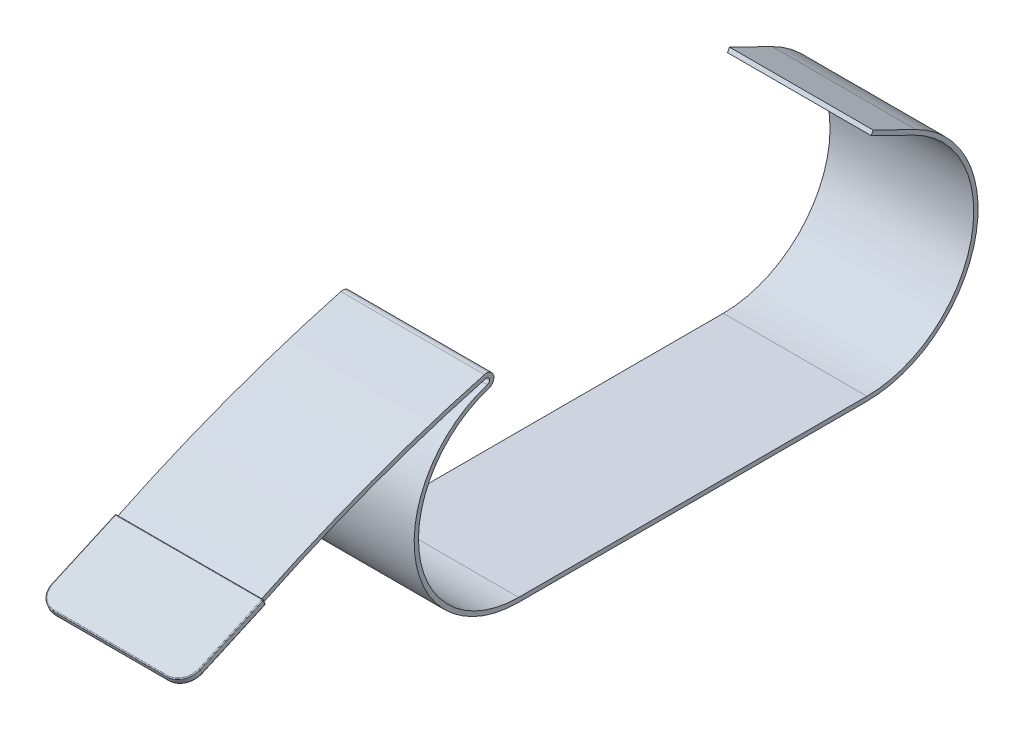
SolidWorks part; units mm, degrees
ref_plane "Front Plane" through (0, 0, 0) normal (0, 0, 1) x (1, 0, 0)
ref_plane "Top Plane" through (0, 0, 0) normal (0, 1, 0) x (1, 0, 0)
ref_plane "Right Plane" through (0, 0, 0) normal (1, 0, 0) x (0, 0, -1)
sketch "Sketch1" plane through (0, 0, 0) normal (1, 0, 0) x (0, 0, -1)
  line L0 (-20, 0) -> (20, 0)
  line L4 (25.3925, 23.2696) -> (20.4877, 25.6719)
  line L5 (-20, -0.5) -> (20, -0.5)
  line L6 (25.6124, 23.7187) -> (20.7076, 26.121)
  line L7 (-49.7729, 14.4908) -> (-49.5556, 14.0405)
  line L8 (20.7076, 26.121) -> (20.4877, 25.6719)
  arc A0 (20, 0) -> (25.3925, 23.2696) centre (20, 12.2596) ccw
  arc A1 (-20, 0) -> (-23.4407, 22.4768) centre (-20, 11.5018) cw
  arc A2 (-23.4407, 22.4768) -> (-23.9201, 24.1215) centre (-23.6969, 23.2943) ccw
  arc A3 (-23.9201, 24.1215) -> (-49.7729, 14.4908) centre (14.7494, -119.1992) ccw
  arc A4 (-23.7899, 23.6387) -> (-49.5556, 14.0405) centre (14.7494, -119.1992) ccw
  arc A5 (-23.5902, 22.9539) -> (-23.7899, 23.6387) centre (-23.6969, 23.2943) ccw
  arc A6 (-20, -0.5) -> (-23.5902, 22.9539) centre (-20, 11.5018) cw
  arc A7 (20, -0.5) -> (25.6124, 23.7187) centre (20, 12.2596) ccw
  dimension "D1" = 40
  dimension "D2" = 0.5
extrude "Boss-Extrude1" add sketch "Sketch1" along normal mid plane 16.5
sketch "Sketch2" plane through (0, 0, 0) normal (1, 0, 0) x (0, 0, -1)
  line L0 (-49.2654, 14.0664) -> (-58.393, 9.9814)
  line L1 (-49.2654, 14.0664) -> (-49.5513, 14.7053)
  line L2 (-58.393, 9.9814) -> (-58.6789, 10.6203)
  line L3 (-49.5513, 14.7053) -> (-58.6789, 10.6203)
  dimension "D1" = 0.7
  dimension "D2" = 10
extrude "Boss-Extrude2" add sketch "Sketch2" along normal mid plane 17
fillet "Fillet2" radius 2 2 edges at (-8.5, 10.3008, 58.5359) (8.5, 10.3008, 58.5359)
sketch "Sketch3" plane through (0, 30.0882, 13.4658) normal (0, -0.9128, -0.4085) x (1, 0, 0)
  line L1 (-6.1992, 48.3368) -> (6.1992, 48.3368)
  line L2 (-7.1992, 47.3368) -> (-7.1992, 44.5095)
  line L3 (-6.1992, 43.5095) -> (6.1992, 43.5095)
  line L4 (7.1992, 47.3368) -> (7.1992, 44.5095)
  line L5 (-7.1992, 48.3368) -> (7.1992, 43.5095) construction
  line L6 (-7.1992, 43.5095) -> (7.1992, 48.3368) construction
  arc A0 (-7.1992, 44.5095) -> (-6.1992, 43.5095) centre (-6.1992, 44.5095) ccw
  arc A1 (-6.1992, 48.3368) -> (-7.1992, 47.3368) centre (-6.1992, 47.3368) ccw
  arc A2 (6.1992, 43.5095) -> (7.1992, 44.5095) centre (6.1992, 44.5095) ccw
  arc A3 (6.1992, 48.3368) -> (7.1992, 47.3368) centre (6.1992, 47.3368) cw
  point P0 (0, 45.9231)
  dimension "D1" = 1
extrude "Cut-Extrude1" cut sketch "Sketch3" against normal blind 0.1
fillet "Fillet1" radius 0.1 22 edges at (-8.5, 13.0713, 53.2024) (-8.5, 12.4324, 52.9164) (-8.5, 14.3858, 49.4084) (0, 10.6203, 58.6789) (0, 9.9814, 58.393) (8.5, 12.4324, 52.9164) (8.5, 13.0713, 53.2024) (8.5, 14.3858, 49.4084) (0, 14.0664, 49.2654) (0, 14.7053, 49.5513) (-7.9142, 10.2207, 57.8583) (7.9142, 10.2207, 57.8583) (-7.9142, 10.8596, 58.1442) (7.9142, 10.8596, 58.1442) (7.1992, 11.3287, 55.3825) (6.9063, 12.195, 53.4468) (0, 12.3146, 53.1794) (-6.9063, 12.195, 53.4468) (-7.1992, 11.3287, 55.3825) (-6.9063, 10.4623, 57.3183) (0, 10.3427, 57.5856) (6.9063, 10.4623, 57.3183)
